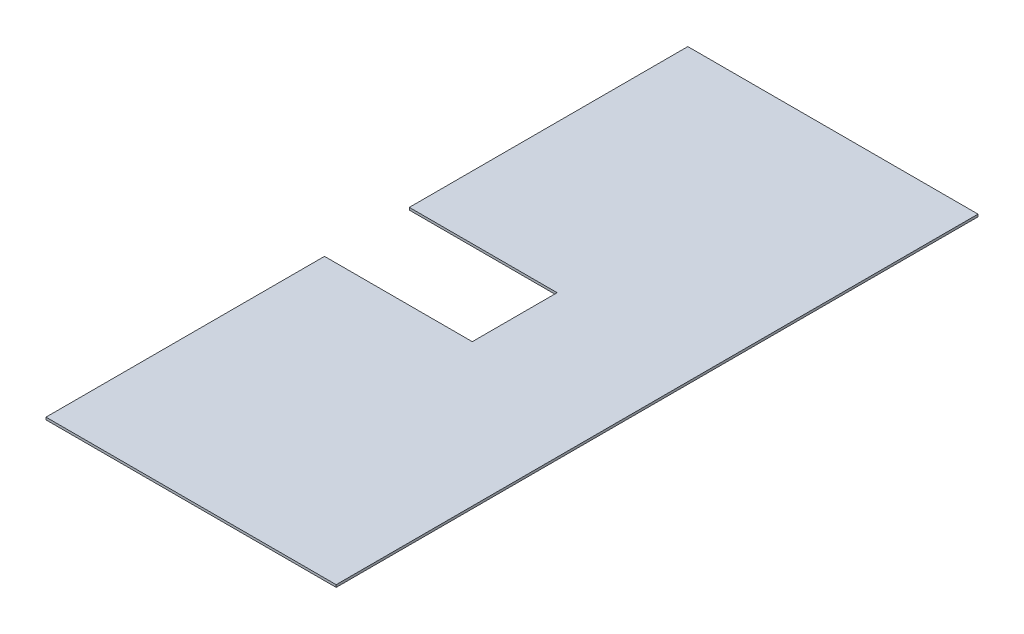
SolidWorks part; units mm, degrees
material "AISI 1020"
ref_plane "Спереди" through (0, 0, 0) normal (0, 0, 1) x (1, 0, 0)
ref_plane "Сверху" through (0, 0, 0) normal (0, 1, 0) x (1, 0, 0)
ref_plane "Справа" through (0, 0, 0) normal (1, 0, 0) x (0, 0, -1)
sketch "Эскиз2" plane through (0, 0, 0) normal (0, 0, 1) x (1, 0, 0)
  line L0 (-362.5978, -13.5) -> (-177.9118, 31.9613) construction
  circle A0 centre (-406.6581, -24.3457) radius 205.5746 construction
  circle A1 centre (-406.6581, -24.3457) radius 235.5746
  dimension "D1" = 30
sketch "Эскиз3" plane through (-357.1721, 0, 0) normal (0, 1, 0) x (1, 0, 0)
  line L0 (8.0743, -48) -> (-18.9257, -48) construction
  line L1 (-5.4257, 401) -> (357.1721, 401)
  line L2 (-5.4257, 401) -> (-5.4257, 53)
  line L3 (-5.4257, -401) -> (357.1721, -401)
  line L4 (357.1721, 401) -> (357.1721, -401)
  line L5 (-5.4257, 53) -> (179.2603, 53)
  line L7 (-5.4257, -53) -> (179.2603, -53)
  line L8 (179.2603, 53) -> (179.2603, -53)
  line L9 (-5.4257, -53) -> (-5.4257, -401)
  line L10 (-5.4257, 0) -> (179.2603, 0) construction
  dimension "D1" = 5
base flange "Базовая кромка1" sketch "Эскиз3" thickness 3 reverse thickness direction yes parameters "D1"=0.74
sketch "Сгиб-Линии1" [suppressed] plane through (0, 0, 0) normal (0, 1, 0) x (1, 0, 0)
sketch "Граничная рамка1" [suppressed] plane through (0, 0, 0) normal (0, 1, 0) x (1, 0, 0)
sheet metal parameters "Листовой металл3" thickness 3 parameters "D1"=0.74
flat pattern "Развертка3" [suppressed]
sketch "Сгиб-Линии2" plane through (0, 0, 0) normal (0, 1, 0) x (1, 0, 0)
sketch3d "Граничная рамка2" [suppressed]
  line L0 (0, -401, 0) -> (0, 401, 0) construction
  line L1 (362.5978, -401, 0) -> (362.5978, 401, 0) construction
  line L2 (0, -401, 0) -> (362.5978, -401, 0) construction
  line L3 (0, 401, 0) -> (362.5978, 401, 0) construction
